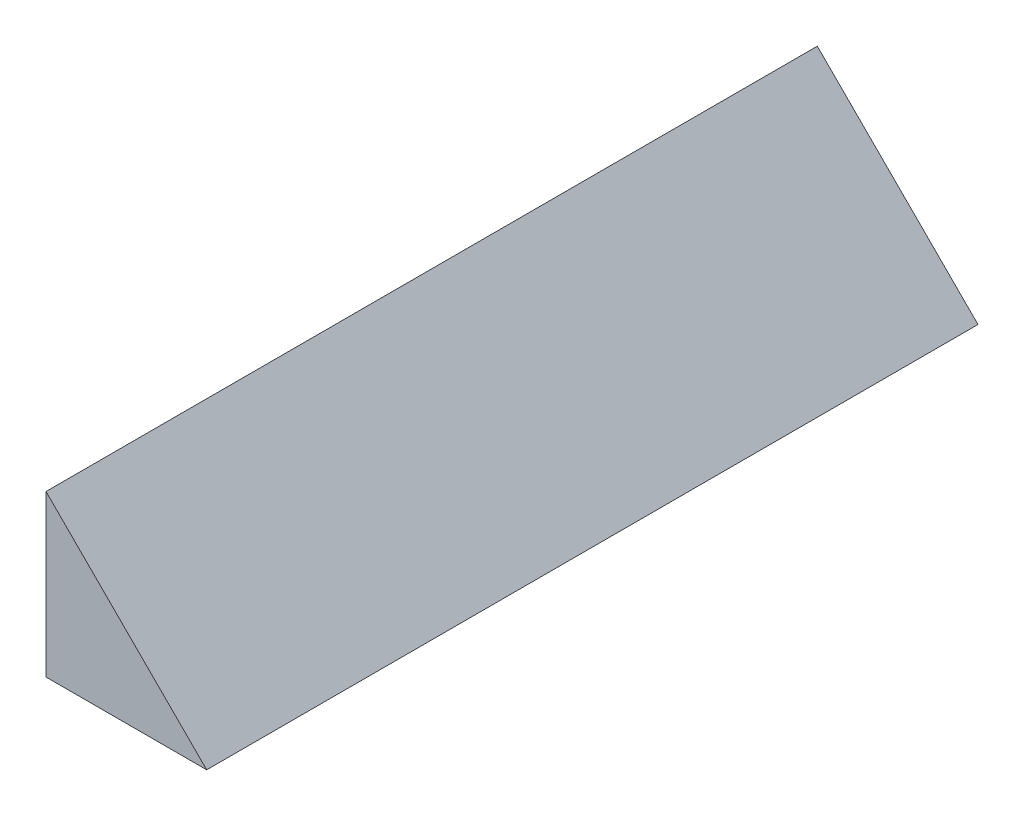
SolidWorks part; units mm, degrees
ref_plane "正面" through (0, 0, 0) normal (0, 0, 1) x (1, 0, 0)
ref_plane "平面" through (0, 0, 0) normal (0, 1, 0) x (1, 0, 0)
ref_plane "右側面" through (0, 0, 0) normal (1, 0, 0) x (0, 0, -1)
sketch "ｽｹｯﾁ1" plane through (0, 0, 0) normal (0, 0, 1) x (1, 0, 0)
  line L1 (0, 0) -> (5, 0)
  line L2 (0, 0) -> (0, 5)
  line L3 (0, 5) -> (5, 5)
  line L4 (5, 0) -> (5, 5)
  dimension "D1" = 5
  dimension "D2" = 5
extrude "ﾎﾞｽ - 押し出し1" add sketch "ｽｹｯﾁ1" along normal blind 24
chamfer "面取り1" distance 5 angle 45 1 edges at (5, 5, 12)
